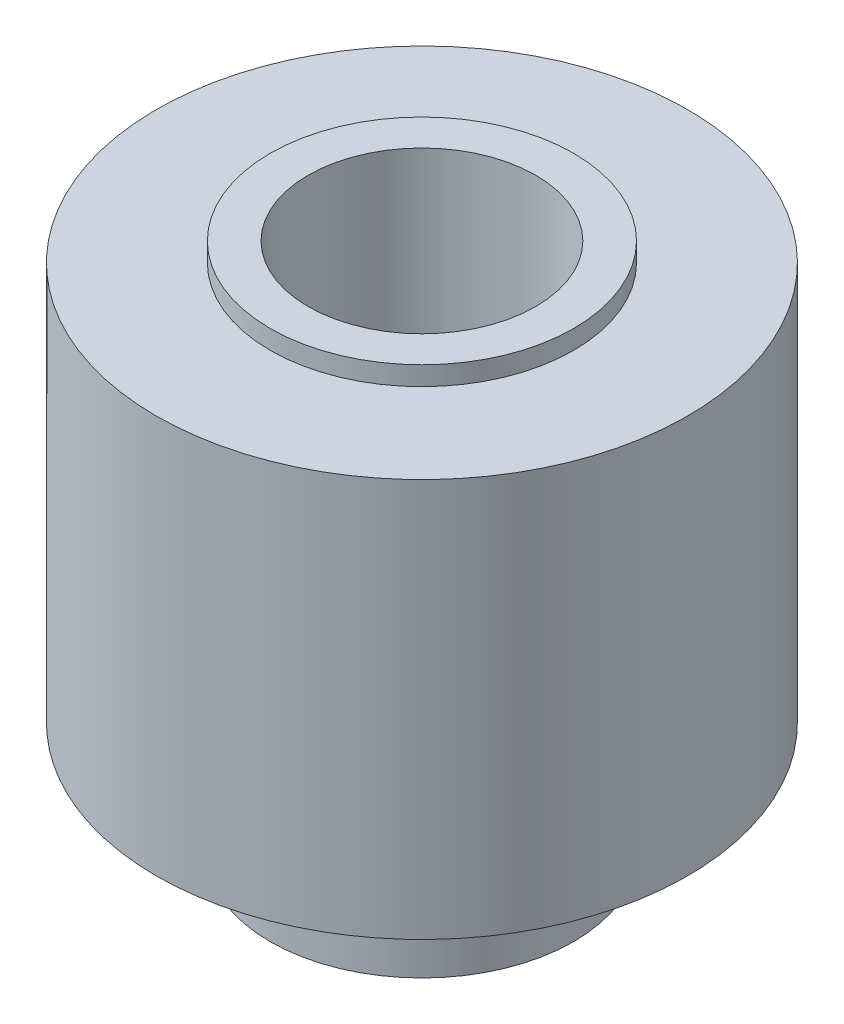
SolidWorks part; units mm, degrees
material "Nylon 101"
ref_plane "Front Plane" through (0, 0, 0) normal (0, 0, 1) x (1, 0, 0)
ref_plane "Top Plane" through (0, 0, 0) normal (0, 1, 0) x (1, 0, 0)
ref_plane "Right Plane" through (0, 0, 0) normal (1, 0, 0) x (0, 0, -1)
sketch "Sketch1" plane through (0, 0, 0) normal (0, 1, 0) x (1, 0, 0)
  circle A0 centre (0, 0) radius 7
  circle A1 centre (0, 0) radius 3
  dimension "D1" = 14
  dimension "D2" = 6
extrude "Boss-Extrude1" add sketch "Sketch1" along normal blind 14
sketch "Sketch2" plane through (0, 0, 0) normal (0, 0, 1) x (1, 0, 0)
  line L0 (-7, 0) -> (7, 0) construction
  line L1 (4, 0) -> (7, 0)
  line L2 (4, 0) -> (4, 3)
  line L3 (4, 3) -> (7, 3)
  line L4 (7, 0) -> (7, 3)
  line L5 (7, 0) -> (7, 14) construction
  line L6 (7, 14) -> (-7, 14) construction
  line L7 (7, 13.5) -> (4, 13.5)
  line L8 (7, 13.5) -> (7, 14)
  line L9 (7, 14) -> (4, 14)
  line L10 (4, 13.5) -> (4, 14)
  dimension "D1" = 3
  dimension "D2" = 0.5
  dimension "D3" = 3
ref_axis "Axis1" through (0, 14, 0) along (0, -1, 0)
revolve "Cut-Revolve1" cut sketch "Sketch2" angle 360 about axis through (0, 14, 0) along (0, -1, 0)
